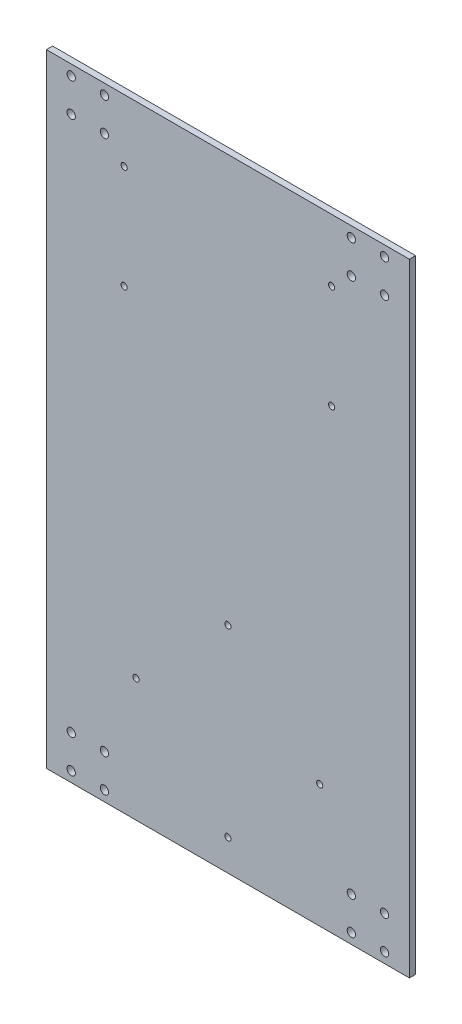
SolidWorks part; units mm, degrees
ref_plane "前视基准面" through (0, 0, 0) normal (0, 0, 1) x (1, 0, 0)
ref_plane "上视基准面" through (0, 0, 0) normal (0, 1, 0) x (1, 0, 0)
ref_plane "右视基准面" through (0, 0, 0) normal (1, 0, 0) x (0, 0, -1)
sketch "草图1" plane through (0, 0, 0) normal (0, 0, 1) x (1, 0, 0)
  line L1 (-87.5, -150) -> (87.5, -150)
  line L2 (-87.5, -150) -> (-87.5, 150)
  line L3 (-87.5, 150) -> (87.5, 150)
  line L4 (87.5, -150) -> (87.5, 150)
  line L5 (-87.5, -150) -> (87.5, 150) construction
  line L6 (-87.5, 150) -> (87.5, -150) construction
  point P0 (0, 0)
extrude "凸台-拉伸1" add sketch "草图1" along normal blind 3
sketch "草图2" plane through (0, 0, 3) normal (0, 0, 1) x (1, 0, 0)
  circle A0 centre (0, -135) radius 1.5
  circle A1 centre (-44.25, -90.75) radius 1.5
  circle A2 centre (0, -46.5) radius 1.5
  circle A3 centre (44.25, -90.75) radius 1.5
  point P18 (0, -90.75)
  dimension "D1" = 4
extrude "切除-拉伸1" cut sketch "草图2" against normal blind 3
sketch "草图3" plane through (0, 0, 3) normal (0, 0, 1) x (1, 0, 0)
  circle A0 centre (50, 70) radius 1.5
  circle A1 centre (50, 120) radius 1.5
  circle A2 centre (-50, 120) radius 1.5
  circle A3 centre (-50, 70) radius 1.5
extrude "切除-拉伸2" cut sketch "草图3" against normal blind 3
sketch "草图4" plane through (0, 0, 3) normal (0, 0, 1) x (1, 0, 0)
  circle A0 centre (-75.5, 145) radius 2
  circle A1 centre (-59.5, 145) radius 2
  circle A2 centre (-59.5, 129) radius 2
  circle A3 centre (-75.5, 129) radius 2
  circle A4 centre (-59.5, -145) radius 2
  circle A5 centre (-75.5, -145) radius 2
  circle A6 centre (-59.5, -129) radius 2
  circle A7 centre (-75.5, -129) radius 2
  circle A8 centre (75.5, -145) radius 2
  circle A9 centre (75.5, -129) radius 2
  circle A10 centre (59.5, -129) radius 2
  circle A11 centre (59.5, -145) radius 2
  circle A12 centre (75.5, 129) radius 2
  circle A13 centre (59.5, 145) radius 2
  circle A14 centre (75.5, 145) radius 2
  circle A15 centre (59.5, 129) radius 2
  point P18 (-67.5, 137)
  dimension "D1" = 4
extrude "切除-拉伸3" cut sketch "草图4" against normal blind 10
